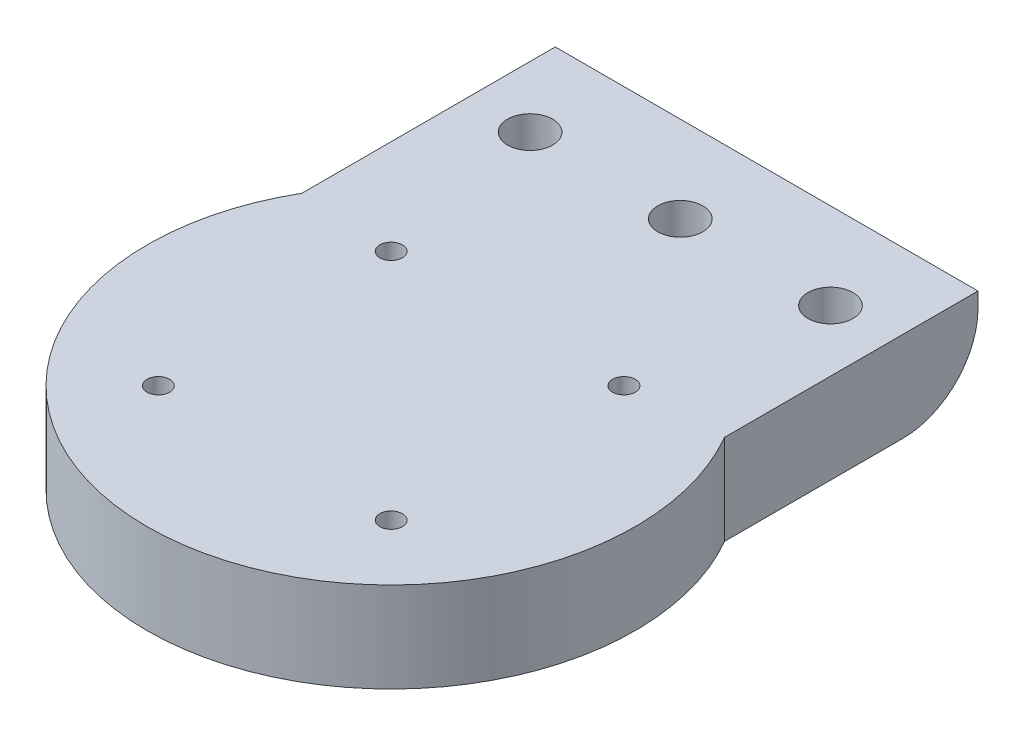
SolidWorks part; units mm, degrees
material "5052-H32"
ref_plane "前视基准面" through (0, 0, 0) normal (0, 0, 1) x (1, 0, 0)
ref_plane "上视基准面" through (0, 0, 0) normal (0, 1, 0) x (1, 0, 0)
ref_plane "右视基准面" through (0, 0, 0) normal (1, 0, 0) x (0, 0, -1)
sketch "草图1" plane through (0, 0, 0) normal (0, 1, 0) x (1, 0, 0)
  line L2 (15.5, 15.5) -> (-15.5, 15.5)
  line L3 (-15.5, 15.5) -> (-15.5, -15.5)
  line L4 (-15.5, -15.5) -> (15.5, -15.5)
  line L5 (15.5, -15.5) -> (15.5, 15.5)
  circle A0 centre (0, 0) radius 32.5
  circle A1 centre (-15.5, 15.5) radius 1.5
  circle A2 centre (15.5, 15.5) radius 1.5
  circle A3 centre (15.5, -15.5) radius 1.5
  circle A4 centre (-15.5, -15.5) radius 1.5
extrude "凸台-拉伸2" add sketch "草图1" along normal blind 12 contours A0 A4 L3 A1 L2 A2 L5 A3 L4 | A4 L4 A3 L5 A2 L2 A1 L3 region at (0, 0, 0) region at (-31.5808, 0, 0)
sketch "草图2" plane through (0, 0, 0) normal (0, -1, 0) x (1, 0, 0)
  circle A0 centre (0, 0) radius 5
extrude "凸台-拉伸3" add sketch "草图2" along normal blind 12
sketch "草图3" plane through (0, 12, 0) normal (0, 1, 0) x (1, 0, 0)
  line L0 (0, 0) -> (28.1458, 16.25)
  line L1 (0, 0) -> (-28.1458, 16.25)
  line L2 (0, 0) -> (0, 50)
  line L3 (0, 50) -> (-28.1458, 50)
  line L4 (-28.1458, 50) -> (-28.1458, 16.25)
  line L5 (0, 50) -> (28.1458, 50)
  line L6 (28.1458, 50) -> (28.1458, 16.25)
  circle A0 centre (0, 0) radius 32.5 construction
  circle M10 centre (0, 0) radius 32.5
extrude "凸台-拉伸4" add sketch "草图3" against normal blind 12 contours L3 L4 L2 M10 | L6 L5 L2 M10 region at (15.6538, 12, -38.4201) region at (-15.6538, 12, -38.4201)
sketch "草图4" plane through (0, 12, 0) normal (0, 1, 0) x (1, 0, 0)
  line L0 (0, 0) -> (0, 32.5)
  line L1 (0, 32.5) -> (28.1458, 32.5)
  line L2 (28.1458, 50) -> (28.1458, 16.25) construction
  line L3 (28.1458, 32.5) -> (28.1458, 44.5)
  line L4 (28.1458, 44.5) -> (-28.1458, 44.5)
  line L5 (-28.1458, 50) -> (-28.1458, 16.25) construction
  line L6 (-28.1458, 44.5) -> (-28.1458, 32.5)
  line L7 (-28.1458, 32.5) -> (0, 32.5)
  line L8 (0, 32.5) -> (0, 44.5)
  line L9 (0, 38.5) -> (20, 38.5)
  line L10 (0, 38.5) -> (-20, 38.5)
  circle A0 centre (0, 0) radius 32.5
  circle A1 centre (0, 38.5) radius 3
  circle A2 centre (20, 38.5) radius 3
  circle A3 centre (-20, 38.5) radius 3
extrude "切除-拉伸1" cut sketch "草图4" against normal blind 12 contours A3 | L8 A1 L9 | L10 A1 L8 | L8 A1 L10 | L9 A1 L8 | A2 region at (20, 12, -41.4151) region at (-22.9151, 12, -38.5) region at (-1.2732, 12, -37.2268) region at (1.2732, 12, -37.2268) region at (-1.2732, 12, -39.7732) region at (1.2732, 12, -39.7732)
fillet "圆角2" radius 10 1 edges at (0, 0, -50)
